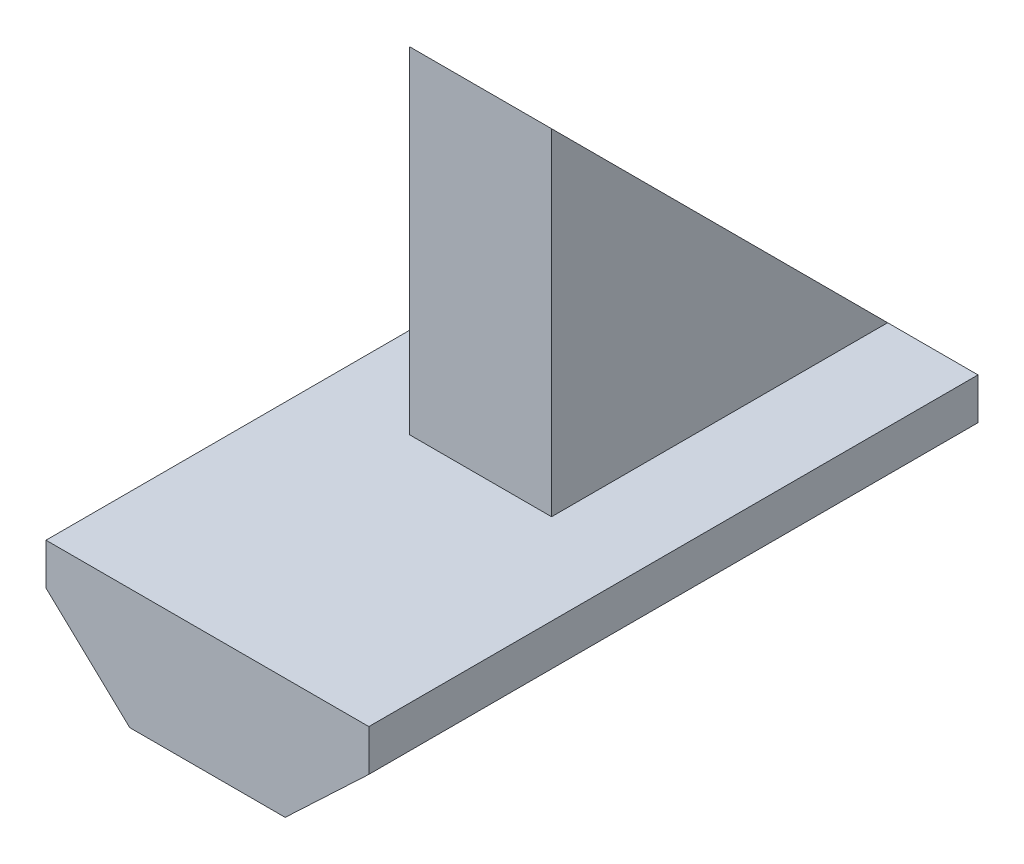
SolidWorks part; units mm, degrees
ref_plane "Front Plane" through (0, 0, 0) normal (0, 0, 1) x (1, 0, 0)
ref_plane "Top Plane" through (0, 0, 0) normal (0, 1, 0) x (1, 0, 0)
ref_plane "Right Plane" through (0, 0, 0) normal (1, 0, 0) x (0, 0, -1)
sketch "Sketch1" plane through (0, 0, 0) normal (0, 0, 1) x (1, 0, 0)
  line L1 (7.95, 0) -> (7.95, -2.04)
  line L2 (7.95, -2.04) -> (3.8283, -5.9337)
  line L6 (3.8283, -5.9337) -> (-3.8283, -5.9337)
  line L7 (0, 0) -> (0, 9.9098) construction
  line L8 (-7.95, -2.04) -> (-3.8283, -5.9337)
  line L9 (-7.95, 0) -> (-7.95, -2.04)
  line L10 (-7.95, 0) -> (7.95, 0)
  point P9 (0, -5.9337)
  dimension "D1" = 15.9
  dimension "D3" = 2.04
  dimension "D4" = 5.67
extrude "Boss-Extrude1" add sketch "Sketch1" along normal blind 30 contours L10 L1 L2 L6 L8 L9
ref_plane "Plane1" through (0, 0, 0) normal (-1, 0, 0) x (0, 0, 1)
sketch "Sketch2" plane through (0, 0, 0) normal (-1, 0, 0) x (0, 0, 1)
  line L0 (0, 0) -> (16.5516, 16.5516)
  line L1 (16.5516, 16.5516) -> (16.5516, 0)
  line L2 (30, 0) -> (0, 0) construction
  line L3 (16.5516, 0) -> (0, 0)
  dimension "D1" = 45
extrude "Boss-Extrude2" add sketch "Sketch2" along normal mid plane 7 contours L3 L0 L1
ref_plane "Plane2" through (0, 3.5355, -3.5355) normal (0, 0.7071, -0.7071) x (-1, 0, 0)
